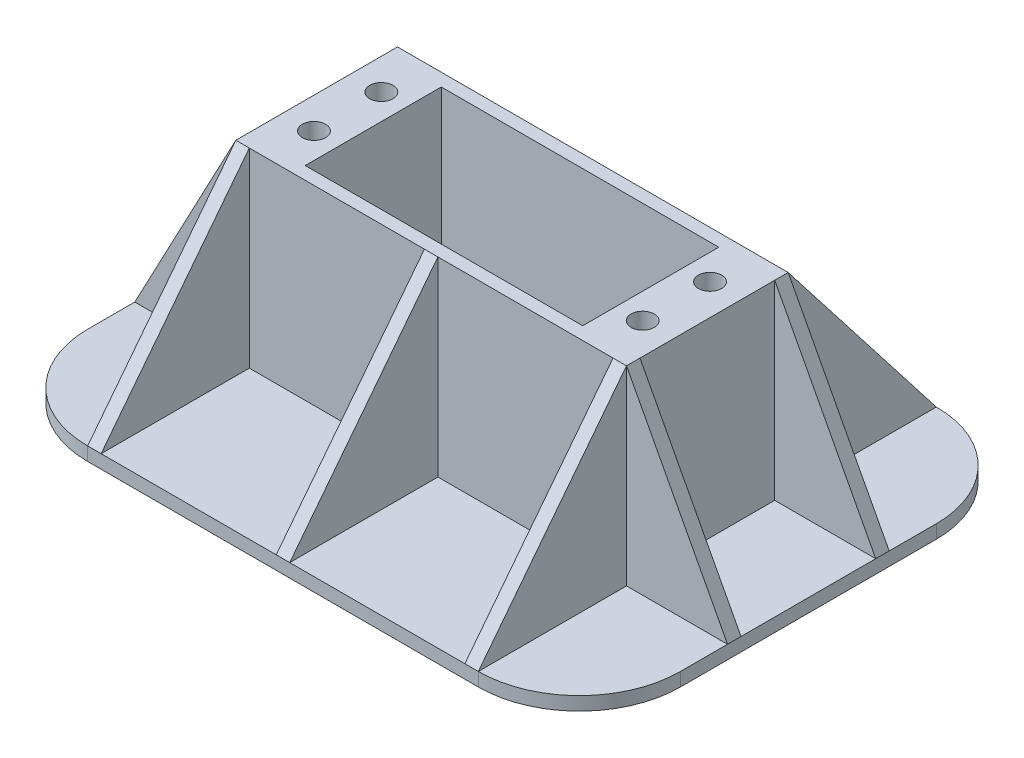
SolidWorks part; units mm, degrees
ref_plane "Front Plane" through (0, 0, 0) normal (0, 0, 1) x (1, 0, 0)
ref_plane "Top Plane" through (0, 0, 0) normal (0, 1, 0) x (1, 0, 0)
ref_plane "Right Plane" through (0, 0, 0) normal (1, 0, 0) x (0, 0, -1)
sketch "Sketch1" plane through (0, 0, 0) normal (0, 1, 0) x (1, 0, 0)
  line L1 (-29, -12) -> (29, -12)
  line L2 (-29, -12) -> (-29, 12)
  line L3 (-29, 12) -> (29, 12)
  line L4 (29, -12) -> (29, 12)
  line L5 (-29, -12) -> (29, 12) construction
  line L6 (-29, 12) -> (29, -12) construction
  point P0 (0, 0)
  dimension "D1" = 24
  dimension "D2" = 58
extrude "Boss-Extrude1" add sketch "Sketch1" along normal blind 28.3
sketch "Sketch2" plane through (0, 0, 0) normal (0, -1, 0) x (1, 0, 0)
  line L1 (-44, -34) -> (44, -34)
  line L2 (-44, -34) -> (-44, 34)
  line L3 (-44, 34) -> (44, 34)
  line L4 (44, -34) -> (44, 34)
  line L5 (-44, -34) -> (44, 34) construction
  line L6 (-44, 34) -> (44, -34) construction
  point P0 (0, 0)
  dimension "D1" = 68
  dimension "D2" = 88
extrude "Boss-Extrude2" add sketch "Sketch2" along normal blind 2
ref_plane "Plane2" through (29, 0, 0) normal (1, 0, 0) x (0, 0, -1)
ref_plane "Plane3" through (-29, 0, 0) normal (-1, 0, 0) x (0, 0, 1)
sketch "Sketch12" plane through (0, 28.3, 0) normal (0, 1, 0) x (1, 0, 0)
  line L1 (-20.6, -10.1) -> (20.6, -10.1)
  line L6 (-20.6, -10.1) -> (-20.6, 10.1)
  line L7 (-20.6, 10.1) -> (20.6, 10.1)
  line L8 (20.6, -10.1) -> (20.6, 10.1)
  line L9 (-20.6, -10.1) -> (20.6, 10.1) construction
  line L10 (-20.6, 10.1) -> (20.6, -10.1) construction
  point P0 (0, 0)
  point P2 (0, 0)
  dimension "D1" = 41.2
  dimension "D2" = 20.2
extrude "Cut-Extrude1" cut sketch "Sketch12" against normal blind 27.95
ref_plane "Plane4" through (-29, 0, 0) normal (-1, 0, 0) x (0, 0, 1)
sketch "Sketch14" plane through (-29, 0, 0) normal (-1, 0, 0) x (0, 0, 1)
  line L0 (-12, 28.3) -> (-12, 0)
  line L1 (-12, 0) -> (-34, 0)
  line L2 (-34, 0) -> (-12, 28.3)
  line L3 (12, 28.3) -> (12, 0)
  line L4 (12, 0) -> (34, 0)
  line L5 (34, 0) -> (12, 28.3)
extrude "Boss-Extrude6" add sketch "Sketch14" against normal blind 2
pattern_linear "LPattern2" count 3 spacing 28 along (1, 0, 0) of "Boss-Extrude6"
ref_plane "Plane5" through (0, 0, -12) normal (0, 0, -1) x (-1, 0, 0)
sketch "Sketch16" plane through (0, 0, -12) normal (0, 0, -1) x (-1, 0, 0)
  line L0 (-29, 28.3) -> (-44, 0)
  line L1 (-44, 0) -> (-29, 0)
  line L2 (-29, 0) -> (-29, 28.3)
  line L3 (29, 28.3) -> (29, 0)
  line L4 (29, 0) -> (44, 0)
  line L5 (44, 0) -> (29, 28.3)
extrude "Boss-Extrude7" add sketch "Sketch16" against normal blind 2
pattern_linear "LPattern3" count 2 spacing 22 along (0, 0, 1) of "Boss-Extrude7"
sketch "Sketch17" plane through (0, 28.3, 0) normal (0, 1, 0) x (1, 0, 0)
  circle A0 centre (-24.4, 5) radius 1
  circle A1 centre (-24.4, -5) radius 1
  circle A2 centre (24.4, -5) radius 1
  circle A3 centre (24.4, 5) radius 1
  dimension "D1" = 2
  dimension "D2" = 2
  dimension "D3" = 2
  dimension "D4" = 2
extrude "Cut-Extrude2" cut sketch "Sketch17" against normal blind 10
hole_wizard "#8-32 Tapped Hole1" positions "3DSketch1" profile "Sketch18" tap size "#8-32" standard "ANSI Inch"
sketch3d "3DSketch1"
  line L0 (-24.4, 18.3, -5) -> (-24.4, 28.3, -5) construction
  line L1 (-24.4, 18.3, 5) -> (-24.4, 28.3, 5) construction
  line L2 (24.4, 18.3, -5) -> (24.4, 28.3, -5) construction
  line L3 (24.4, 18.3, 5) -> (24.4, 28.3, 5) construction
  point P0 (-24.4, 28.3, -5)
  point P4 (-24.4, 28.3, 5)
  point P8 (24.4, 28.3, -5)
  point P12 (24.4, 28.3, 5)
cosmetic thread "Hole Thread1" parameters "D1"=10.75, "D2"=4.1656
cosmetic thread "Hole Thread2" parameters "D1"=10.75, "D2"=4.1656
cosmetic thread "Hole Thread3" parameters "D1"=10.75, "D2"=4.1656
cosmetic thread "Hole Thread4" parameters "D1"=10.75, "D2"=4.1656
sketch "Sketch18" plane through (-24.4, 28.3, -5) normal (1, 0, 0) x (0, 0, 1)
  line L0 (0, 0) -> (0, 13.0378)
  line L1 (0, 13.0378) -> (1.7272, 12)
  line L2 (1.7272, 12) -> (1.7272, 0)
  line L5 (1.7272, 0) -> (0, 0)
  line L10 (0, 13.0378) -> (-1.7272, 12) construction
  line L11 (0, -6.35) -> (0, 107.95) construction
  dimension "Tap Drill Dia." = 3.4544
  dimension "Tap Drill Depth" = 12
  dimension "Drill Angle" = 118
fillet "Fillet1" radius 15 1 edges at (-44, -1, 34) type face fillet first side face at (-44, -0.5, 0) second side face at (0, -0.4, 34)
fillet "Fillet2" radius 15 1 edges at (44, -1, 34) type face fillet first side face at (44, -0.5, 0) second side face at (6.5556, -0.4444, 34)
fillet "Fillet3" radius 15 1 edges at (44, -1, -34) type face fillet first side face at (44, -0.5, -3.75) second side face at (0, -0.4, -34)
fillet "Fillet5" radius 15 1 edges at (-44, -1, -34) type face fillet first side face at (-44, -0.5, -3.75) second side face at (-6.5556, -0.4444, -34)
